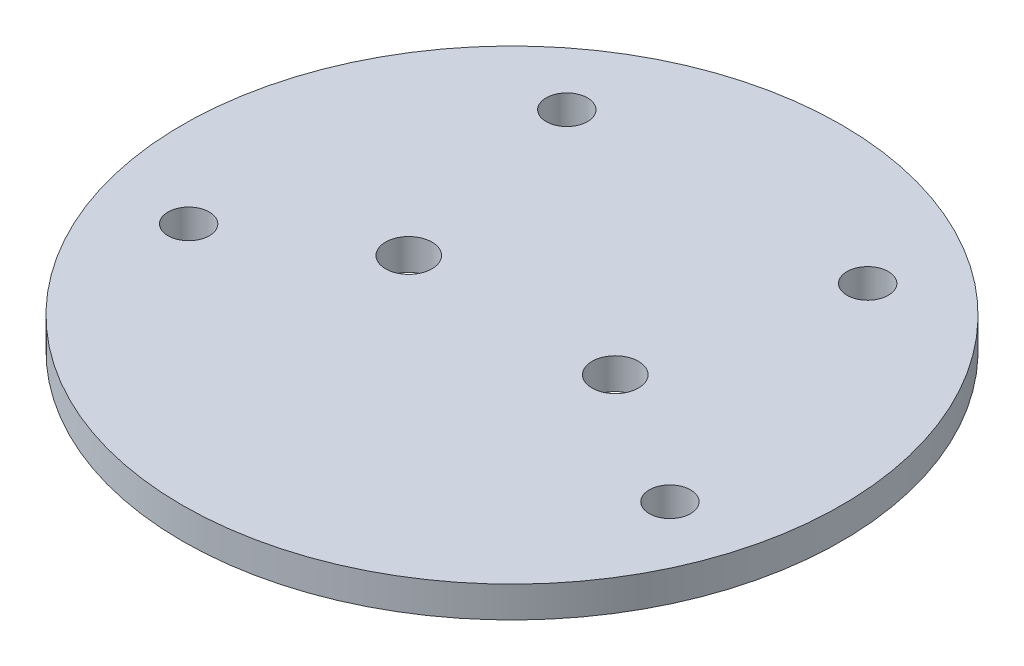
SolidWorks part; units mm, degrees
material "5052-H32"
ref_plane "Front Plane" through (0, 0, 0) normal (0, 0, 1) x (1, 0, 0)
ref_plane "Top Plane" through (0, 0, 0) normal (0, 1, 0) x (1, 0, 0)
ref_plane "Right Plane" through (0, 0, 0) normal (1, 0, 0) x (0, 0, -1)
sketch "Sketch1" plane through (0, 0, 0) normal (0, 1, 0) x (1, 0, 0)
  line L0 (0, 0) -> (-23.1297, 31.5565) construction
  line L1 (0, 0) -> (-41.7254, 0) construction
  line L2 (-37.0005, -12.7186) -> (0, 0) construction
  line L3 (0, -31.6103) -> (0, 47.1695) construction
  circle A0 centre (0, 0) radius 50.673
  circle A3 centre (-15.875, 0) radius 3.5687
  circle A4 centre (15.875, 0) radius 3.5687
  circle A5 centre (-37.0005, -12.7186) radius 3.175
  circle A8 centre (-23.1297, 31.5565) radius 3.175
  circle A9 centre (23.1297, 31.5565) radius 3.175
  circle A10 centre (37.0005, -12.7186) radius 3.175
  dimension "D1" = 101.346
  dimension "D2" = 6.35
  dimension "D3" = 6.35
  dimension "D5" = 15.875
  dimension "D6" = 15.875
  dimension "D4" = 39.1254
  dimension "D7" = 53.76
  dimension "D8" = 39.1254
  dimension "D9" = 18.97
extrude "Boss-Extrude1" add sketch "Sketch1" along normal blind 4.7752
equation "\"allrockets_tube_ID\"= 3.85in"
equation "\"allrockets_tube_OD\"= 4.024in"
equation "\"hole\"= 6.35mm"
equation "\"back_plate_width\"= 28mm"
equation "\"card_spacing\"= 15.41mm"
equation "\"card_number\"= 6"
equation "\"ToDi\"= 0.05mm"
equation "\"card_diameter\"= 85.86mm"
equation "\"overlap\"= 6.6mm"
equation "\"card_length\"= 68mm"
equation "\"rack_hole_tol\"= 0.35mm"
equation "\"rack_front_width\"= 11.63mm"
equation "\"hole_b_d\"= 39.12541885mm"
equation "\"hole_b_a\"= 18.9721389deg"
equation "\"hole_u_d\"= 39.12541885mm"
equation "\"hole_u_a\"= 53.76090642deg"
equation "\"card_h\"= 61.73mm"
equation "\"sphinx_av\"= 50.292mm"
equation "\"tb_spacing\"= 40mm"
equation "\"D2@Sketch1\"=\"hole\""
equation "\"D4@Sketch1\"=\"hole_u_d\""
equation "\"D7@Sketch1\"=\"hole_u_a\""
equation "\"D8@Sketch1\"=\"hole_b_d\""
equation "\"D9@Sketch1\"=\"hole_b_a\""
